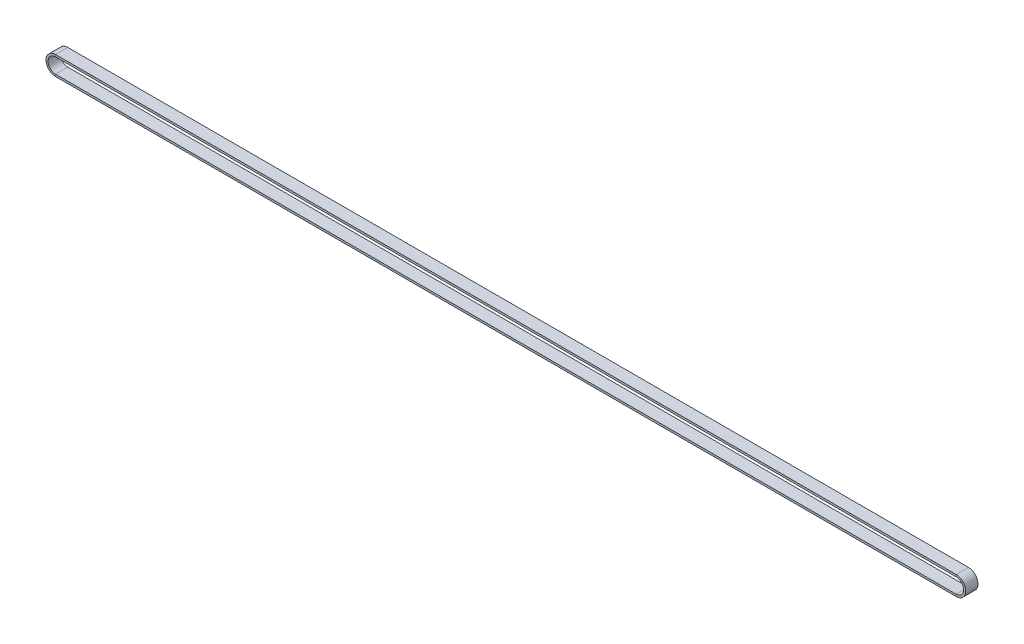
SolidWorks part; units mm, degrees
ref_plane "Front Plane" through (0, 0, 0) normal (0, 0, 1) x (1, 0, 0)
ref_plane "Top Plane" through (0, 0, 0) normal (0, 1, 0) x (1, 0, 0)
ref_plane "Right Plane" through (0, 0, 0) normal (1, 0, 0) x (0, 0, -1)
sketch "Sketch2" plane through (0, 0, 0) normal (0, 0, 1) x (1, 0, 0)
  line L0 (0, 0) -> (1, 0) construction
  line L1 (0, 0) -> (0, 1) construction
  line L2 (0, -7) -> (-660.3327, -7)
  line L3 (-660.3327, 7) -> (0, 7)
  arc A0 (0, 7) -> (0, -7) centre (0, 0) cw
  arc A1 (-660.3327, -7) -> (-660.3327, 7) centre (-660.3327, 0) cw
sketch "Sketch3" plane through (0, 0, 0) normal (1, 0, 0) x (0, 0, -1)
  line L0 (0, 7) -> (0, -7) construction
  line L1 (0, 7) -> (-9, 7)
  line L2 (0, 7) -> (0, 5.5)
  line L3 (0, 5.5) -> (-9, 5.5)
  line L4 (-9, 7) -> (-9, 5.5)
  dimension "D1" = 1.5
  dimension "D2" = 9
sweep "Sweep1" add profiles "Sketch3" path "Sketch2"
move or copy body "Body-Move/Copy1" [suppressed] bodies to move or copy 101
